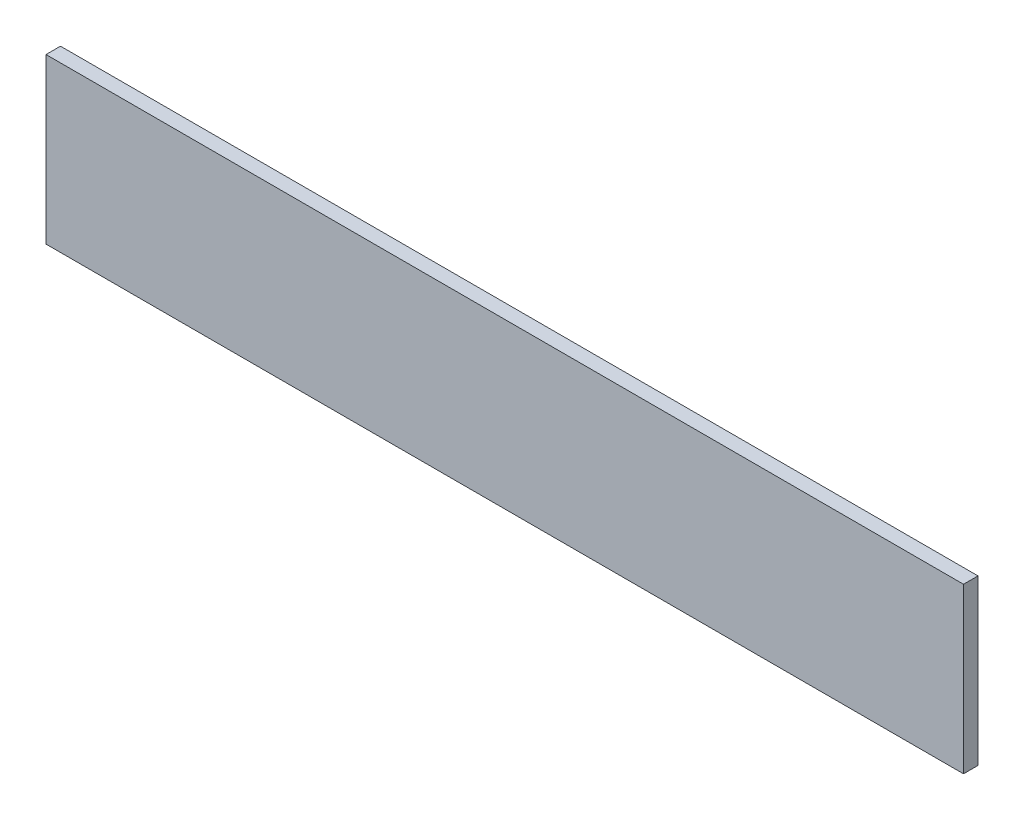
SolidWorks part; units mm, degrees
ref_plane "Front Plane" through (0, 0, 0) normal (0, 0, 1) x (1, 0, 0)
ref_plane "Top Plane" through (0, 0, 0) normal (0, 1, 0) x (1, 0, 0)
ref_plane "Right Plane" through (0, 0, 0) normal (1, 0, 0) x (0, 0, -1)
sketch "Sketch1" plane through (0, 0, 0) normal (0, 0, 1) x (1, 0, 0)
  line L1 (0, 0) -> (190, 0)
  line L2 (0, 0) -> (0, 34)
  line L3 (0, 34) -> (190, 34)
  line L4 (190, 0) -> (190, 34)
  dimension "D1" = 34
  dimension "D2" = 190
sheet metal parameters "Sheet-Metal1" thickness 3 parameters "D1"=0.7366
base flange "Base-Flange1" sketch "Sketch1" thickness 3 reverse thickness direction no parameters "D1"=0.7366
flat pattern "Flat-Pattern1" [suppressed]
sketch "Bend-Lines1" plane through (0, 0, 0) normal (0, 1, 0) x (1, 0, 0)
sketch3d "Bounding-Box1" [suppressed]
  line L0 (0, 0, 0) -> (-190, 0, 0) construction
  line L1 (0, 28, 0) -> (-190, 28, 0) construction
  line L2 (0, 0, 0) -> (0, 28, 0) construction
  line L3 (-190, 0, 0) -> (-190, 28, 0) construction
